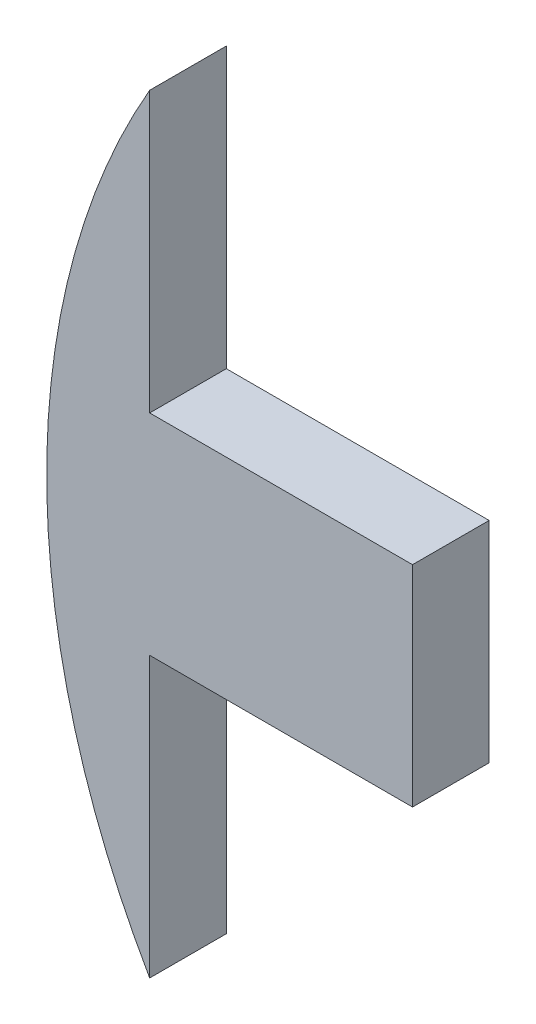
SolidWorks part; units mm, degrees
ref_plane "Front Plane" through (0, 0, 0) normal (0, 0, 1) x (1, 0, 0)
ref_plane "Top Plane" through (0, 0, 0) normal (0, 1, 0) x (1, 0, 0)
ref_plane "Right Plane" through (0, 0, 0) normal (1, 0, 0) x (0, 0, -1)
sketch "Sketch4" plane through (0, 0, 0) normal (0, 0, 1) x (1, 0, 0)
  line L43 (-10.5471, -11.2309) -> (-10.5471, -0.1809)
  line L44 (-10.5471, -0.1809) -> (-0.1547, -0.1809)
  line L45 (-10.5471, 8.1191) -> (-0.1547, 8.1191)
  line L46 (-10.5471, 19.1691) -> (-10.5471, 8.1191)
  line L47 (-0.1547, -0.1809) -> (-0.1547, 8.1191)
  arc A15 (-10.5471, 19.1691) -> (-10.5471, -11.2309) centre (15.7801, 3.9691) ccw
extrude "Boss-Extrude2" add sketch "Sketch4" along normal blind 3.03 contours L46 A15 L43 L44 L47 L45 region at (-8.7173, 3.9691, 0)
